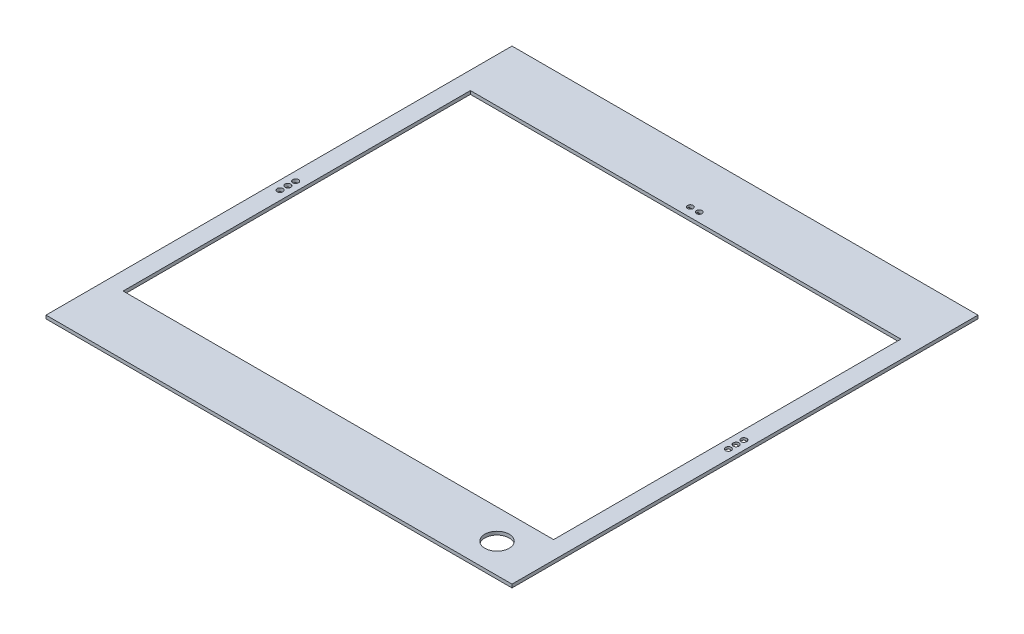
SolidWorks part; units mm, degrees
ref_plane "Front Plane" through (0, 0, 0) normal (0, 0, 1) x (1, 0, 0)
ref_plane "Top Plane" through (0, 0, 0) normal (0, 1, 0) x (1, 0, 0)
ref_plane "Right Plane" through (0, 0, 0) normal (1, 0, 0) x (0, 0, -1)
sketch "Sketch1" plane through (0, 0, 0) normal (0, 1, 0) x (1, 0, 0)
  line L1 (-210, -210) -> (210, -210)
  line L2 (-210, -210) -> (-210, 210)
  line L3 (-210, 210) -> (210, 210)
  line L4 (210, -210) -> (210, 210)
  line L5 (-210, -210) -> (210, 210) construction
  line L6 (-210, 210) -> (210, -210) construction
  line L7 (-194, 156.5) -> (194, 156.5)
  line L8 (-194, 156.5) -> (-194, -156.5)
  line L9 (-194, -156.5) -> (194, -156.5)
  line L10 (194, 156.5) -> (194, -156.5)
  line L11 (-194, 156.5) -> (194, -156.5) construction
  line L12 (-194, -156.5) -> (194, 156.5) construction
  circle A0 centre (169.75, -183.25) radius 11
  point P0 (0, 0)
  point P5 (0, 0)
  dimension "D5" = 22
  dimension "D1" = 420
  dimension "D2" = 420
  dimension "D3" = 313
  dimension "D4" = 388
extrude "Boss-Extrude1" add sketch "Sketch1" along normal blind 3
sketch "Sketch2" plane through (0, 0, 0) normal (0, -1, 0) x (1, 0, 0)
  line L0 (-210, 232.7824) -> (-210, -294.5834) construction
  line L1 (-210, -294.5834) -> (-202, -294.5834) construction
  line L2 (-202, -294.5834) -> (-202, 232.7824) construction
  line L3 (-202, 232.7824) -> (-210, 232.7824) construction
  line L4 (202, 232.7824) -> (202, -294.5834) construction
  line L5 (202, -294.5834) -> (210, -294.5834) construction
  line L6 (210, -294.5834) -> (210, 232.7824) construction
  line L7 (210, 232.7824) -> (202, 232.7824) construction
  line L8 (-197.5, 162.5) -> (-197.5, -162.5) construction
  line L9 (-197.5, -162.5) -> (197.5, -162.5) construction
  line L10 (197.5, -162.5) -> (197.5, 162.5) construction
  line L11 (197.5, 162.5) -> (-197.5, 162.5) construction
  line L12 (-210, 232.7824) -> (-210, -294.5834)
  line L13 (-210, -294.5834) -> (-202, -294.5834)
  line L14 (-202, -294.5834) -> (-202, 232.7824)
  line L15 (-202, 232.7824) -> (-210, 232.7824)
  line L16 (202, 232.7824) -> (202, -294.5834)
  line L17 (202, -294.5834) -> (210, -294.5834)
  line L18 (210, -294.5834) -> (210, 232.7824)
  line L19 (210, 232.7824) -> (202, 232.7824)
  line L20 (-197.5, 162.5) -> (-197.5, -162.5)
  line L21 (-197.5, -162.5) -> (197.5, -162.5)
  line L22 (197.5, -162.5) -> (197.5, 162.5)
  line L23 (197.5, 162.5) -> (-197.5, 162.5)
  line L24 (197.5, -162.5) -> (202, -167) construction
  line L25 (0, 0) -> (0, -113.1665) construction
  line L26 (0, 0) -> (113.3083, 0) construction
  line L27 (197.5, 162.5) -> (202, 167) construction
  line L28 (-197.5, 162.5) -> (-202, 167) construction
  line L29 (-197.5, -162.5) -> (-202, -167) construction
  line L30 (199.75, -164.75) -> (-199.75, -164.75)
  line L31 (-199.75, -164.75) -> (-199.75, 164.75)
  line L32 (-199.75, 164.75) -> (199.75, 164.75)
  line L33 (199.75, 164.75) -> (199.75, -164.75)
  line L34 (201.25, 166.25) -> (201.25, -166.25)
  line L35 (201.25, -166.25) -> (-201.25, -166.25)
  line L36 (-201.25, -166.25) -> (-201.25, 166.25)
  line L37 (-201.25, 166.25) -> (201.25, 166.25)
  line L38 (198.25, 163.25) -> (198.25, -163.25)
  line L39 (198.25, -163.25) -> (-198.25, -163.25)
  line L40 (-198.25, -163.25) -> (-198.25, 163.25)
  line L41 (-198.25, 163.25) -> (198.25, 163.25)
  dimension "D1" = 45
  dimension "D2" = 1.5
  dimension "D3" = 1.5
extrude "Cut-Extrude1" cut sketch "Sketch2" against normal blind 1 contours L37 L36 L35 L34 L32 L33 L30 L31 | L33 L32 L31 L30 L40 L41 L38 L39 region at (0, 0, -164.2321) region at (200.7279, 0, 0)
sketch "Sketch3" plane through (0, 0, 0) normal (0, -1, 0) x (1, 0, 0)
  line L0 (0, -166.25) -> (0, -163.25) construction
  line L1 (198.25, -163.25) -> (-198.25, -163.25) construction
  line L2 (0, -164.75) -> (4, -164.75) construction
  line L4 (201.25, 166.25) -> (-201.25, 166.25)
  line L5 (-201.25, 166.25) -> (-201.25, -166.25)
  line L6 (-201.25, -166.25) -> (201.25, -166.25)
  line L7 (201.25, -166.25) -> (201.25, 166.25)
  line L8 (201.25, 166.25) -> (-201.25, 166.25)
  line L9 (-201.25, 166.25) -> (-201.25, -166.25)
  line L10 (-201.25, -166.25) -> (201.25, -166.25)
  line L11 (201.25, -166.25) -> (201.25, 166.25)
  circle A0 centre (4, -164.75) radius 2.5
  circle A1 centre (-4, -164.75) radius 2.5
  dimension "D2" = 5
  dimension "D3" = 4
  dimension "D1" = 0
extrude "Cut-Extrude2" cut sketch "Sketch3" against normal up to surface (3 mm away) contours L10 A0 | L10 A0 | A1 L10 | A1 L10 region at (4, 0, -166.6578) region at (4, 0, -164.4333) region at (-4, 0, -164.4333) region at (-4, 0, -166.6578) up to face at (0, 3, 0)
sketch "Sketch5" plane through (0, 3, 0) normal (0, 1, 0) x (1, 0, 0)
  line L0 (-194, 0) -> (-210, 0) construction
  line L1 (-194, 156.5) -> (-194, -156.5) construction
  line L2 (-202, 0) -> (-202, 7) construction
  line L3 (-202, 0) -> (-202, -7) construction
  line L4 (210, -210) -> (210, 210)
  line L5 (-210, -210) -> (210, -210)
  line L6 (-210, 210) -> (-210, -210)
  line L7 (210, 210) -> (-210, 210)
  line L8 (210, -210) -> (210, 210)
  line L9 (-210, -210) -> (210, -210)
  line L10 (-210, 210) -> (-210, -210)
  line L11 (210, 210) -> (-210, 210)
  line L12 (0, 156.5) -> (0, -156.5) construction
  line L13 (194, 156.5) -> (-194, 156.5) construction
  line L14 (-194, -156.5) -> (194, -156.5) construction
  circle A0 centre (-202, 0) radius 2.6
  circle A1 centre (-202, 7) radius 2.6
  circle A2 centre (-202, -7) radius 2.6
  circle A3 centre (202, -7) radius 2.6
  circle A4 centre (202, 0) radius 2.6
  circle A5 centre (202, 7) radius 2.6
  dimension "D2" = 5.2
  dimension "D4" = 5.2
  dimension "D6" = 5.2
  dimension "D3" = 7
  dimension "D5" = 7
  dimension "D1" = 0
extrude "Cut-Extrude8" cut sketch "Sketch5" against normal up to surface (3 mm away) contours A2 | A0 | A1 | A3 | A4 | A5 region at (-202, 3, 0) region at (-202, 3, -7) region at (-202, 3, 7) region at (202, 3, 7) region at (202, 3, 0) region at (202, 3, -7) up to face at (169.75, 0, 194.25)
